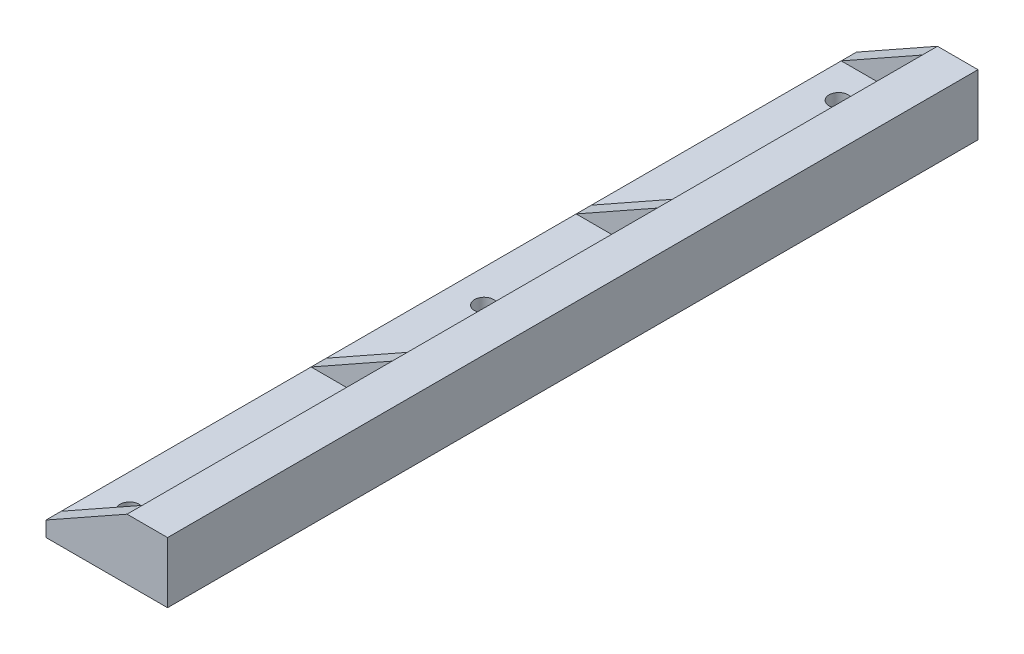
SolidWorks part; units mm, degrees
ref_plane "Front Plane" through (0, 0, 0) normal (0, 0, 1) x (1, 0, 0)
ref_plane "Top Plane" through (0, 0, 0) normal (0, 1, 0) x (1, 0, 0)
ref_plane "Right Plane" through (0, 0, 0) normal (1, 0, 0) x (0, 0, -1)
sketch "Sketch1" plane through (0, 0, 0) normal (0, 0, 1) x (1, 0, 0)
  line L0 (0, 0) -> (0, 12)
  line L1 (0, 12) -> (-8, 12)
  line L2 (-8, 12) -> (-8, 6)
  line L3 (-11, 3) -> (-24, 3)
  line L4 (-24, 3) -> (-24, 0)
  line L5 (-24, 0) -> (0, 0)
  arc A0 (-8, 6) -> (-11, 3) centre (-11, 6) cw
  point P4 (0, 0)
  dimension "D1" = 3
  dimension "D2" = 12
  dimension "D3" = 24
  dimension "D4" = 8
  dimension "D5" = 3
extrude "Boss-Extrude1" add sketch "Sketch1" along normal blind 160
ref_plane "Plane2" through (0, 0, 0) normal (0, 0, -1) x (-1, 0, 0)
ref_plane "Plane3" through (0, 0, 80) normal (0, 0, -1) x (-1, 0, 0)
ref_plane "Plane4" through (0, 0, 53.8333) normal (0, 0, -1) x (-1, 0, 0)
sketch "Sketch4" plane through (0, 0, 53.8333) normal (0, 0, -1) x (-1, 0, 0)
  line L0 (8, 12) -> (24, 3)
sketch "Sketch5" plane through (0, 0, 0) normal (0, 0, -1) x (-1, 0, 0)
  line L0 (8, 12) -> (24, 3)
rib "Rib3" sketch "Sketch4" sketch "Sketch4" thickness 3 extrusion direction parallel to sketch draft on no parameters "D1"=3
rib "Rib4" sketch "Sketch5" sketch "Sketch5" thickness 3 extrusion direction parallel to sketch draft on no parameters "D1"=3
mirror "Mirror1" about plane through (0, 0, 80) normal (0, 0, -1) of "Rib4", "Rib3"
sketch "Sketch7" plane through (0, 0, 0) normal (0, -1, 0) x (1, 0, 0)
  point P0 (-17.4997, 150)
  point P1 (-17.4997, 80)
  point P3 (-17.4997, 10)
hole_wizard "#6 Clearance Hole1" positions "Sketch8" profile "Sketch9" hole size "#6" standard "ANSI Inch" end condition through all
sketch "Sketch8" plane through (0, 0, 0) normal (0, -1, 0) x (-1, 0, 0)
  point P0 (17.4997, -10)
  point P3 (17.4997, -80)
  point P6 (17.4997, -150)
sketch "Sketch9" plane through (-17.4997, 0, 10) normal (1, 0, 0) x (0, 0, -1)
  line L0 (0, 0) -> (0, 12)
  line L1 (0, 12) -> (1.8986, 12)
  line L2 (1.8986, 12) -> (1.8986, 0)
  line L5 (1.8986, 0) -> (0, 0)
  line L11 (0, -6.35) -> (0, 107.95) construction
  dimension "Thru Hole Dia." = 3.7973
  dimension "Thru Hole Depth" = 12
sketch "Sketch10" plane through (0, 0, 0) normal (0, -1, 0) x (-1, 0, 0)
  point P0 (4.2499, -117.6667)
  point P1 (4.2499, -42.3333)
hole_wizard "Tap Drill for M3x0.5 Tap1" positions "Sketch11" profile "Sketch12" hole size "M3x0.5" standard "ANSI Metric"
sketch "Sketch11" plane through (0, 0, 0) normal (0, -1, 0) x (-1, 0, 0)
  point P0 (4.2499, -42.3333)
  point P3 (4.2499, -117.6667)
sketch "Sketch12" plane through (-4.2499, 0, 42.3333) normal (1, 0, 0) x (0, 0, -1)
  line L0 (0, 0) -> (0, 5.7511)
  line L1 (0, 5.7511) -> (1.25, 5)
  line L2 (1.25, 5) -> (1.25, 0)
  line L5 (1.25, 0) -> (0, 0)
  line L10 (0, 5.7511) -> (-1.25, 5) construction
  line L11 (0, -6.35) -> (0, 107.95) construction
  dimension "Hole Dia." = 2.5
  dimension "Hole Depth" = 5
  dimension "Drill Angle" = 118
